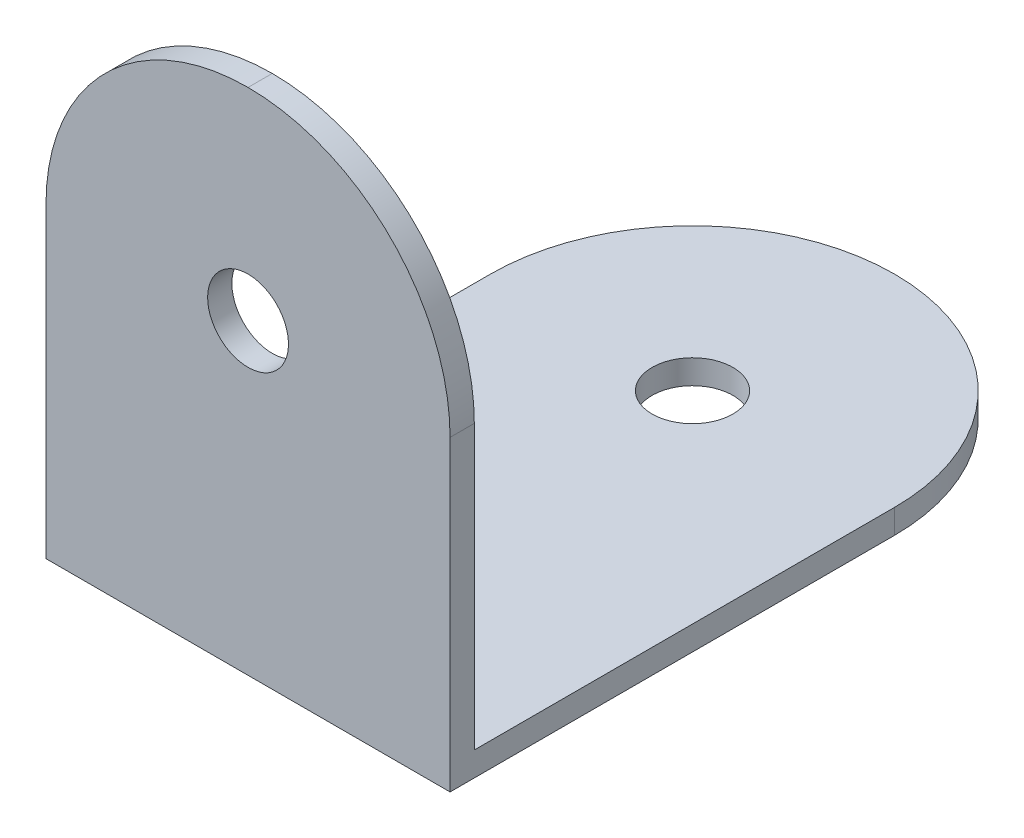
SolidWorks part; units mm, degrees
ref_plane "Front Plane" through (0, 0, 0) normal (0, 0, 1) x (1, 0, 0)
ref_plane "Top Plane" through (0, 0, 0) normal (0, 1, 0) x (1, 0, 0)
ref_plane "Right Plane" through (0, 0, 0) normal (1, 0, 0) x (0, 0, -1)
sketch "Sketch1" plane through (0, 0, 0) normal (0, 1, 0) x (1, 0, 0)
  line L0 (-12.5, -18.5) -> (12.5, -18.5)
  line L1 (12.5, -20) -> (-12.5, -20)
  line L2 (12.5, -20) -> (12.5, 20)
  line L3 (12.5, 20) -> (-12.5, 20)
  line L4 (-12.5, -20) -> (-12.5, 20)
  line L5 (12.5, -20) -> (-12.5, 20) construction
  line L6 (12.5, 20) -> (-12.5, -20) construction
  point P0 (0, 0)
  dimension "D1" = 25
  dimension "D2" = 40
  dimension "D3" = 1.5
extrude "Boss-Extrude1" add sketch "Sketch1" against normal blind 1.5 contours L4 L0 L2 L3 | L4 L1 L2 L0 region at (0, 0, -0.75) region at (0, 0, 19.25)
extrude "Boss-Extrude2" add sketch "Sketch1<3>" along normal blind 30 contours L4 L1 L2 L0 region at (0, 0, 19.25)
sketch "Sketch1<3>" plane through (0, 0, 0) normal (0, 1, 0) x (1, 0, 0) same geometry as "Sketch1"
fillet "Fillet1" radius 12.5 4 edges at (-12.5, 30, 19.25) (12.5, 30, 19.25) (-12.5, -0.75, -20) (12.5, -0.75, -20)
sketch "Sketch2" plane through (0, 0, 0) normal (0, 1, 0) x (1, 0, 0)
  circle A0 centre (0, 7.5) radius 2.5
extrude "Cut-Extrude1" cut sketch "Sketch2" against normal through all
sketch "Sketch3" plane through (0, 0, 18.5) normal (0, 0, -1) x (-1, 0, 0)
  circle A0 centre (0, 17.5) radius 2.5
  dimension "D1" = 5
extrude "Cut-Extrude2" cut sketch "Sketch3" against normal through all both and the other way through all
